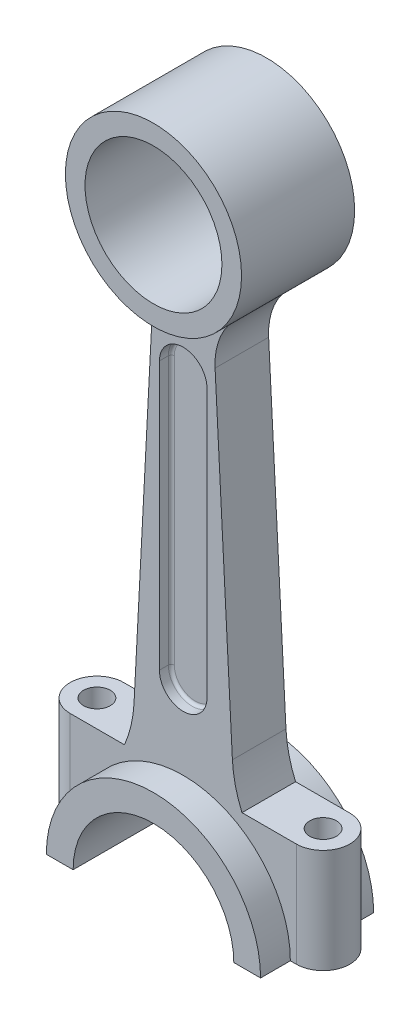
SolidWorks part; units mm, degrees
ref_plane "Front Plane" through (0, 0, 0) normal (0, 0, 1) x (1, 0, 0)
ref_plane "Top Plane" through (0, 0, 0) normal (0, 1, 0) x (1, 0, 0)
ref_plane "Right Plane" through (0, 0, 0) normal (1, 0, 0) x (0, 0, -1)
sketch "Sketch1" plane through (0, 0, 0) normal (0, 0, 1) x (1, 0, 0)
  line L0 (0, 0) -> (0, -201.2) construction
  line L1 (-10, -27.865) -> (-17.4334, -169.7028)
  line L2 (10, -27.865) -> (17.4334, -169.7028)
  line L3 (-36, -201.2) -> (-27, -201.2)
  line L4 (27, -201.2) -> (36, -201.2)
  circle A0 centre (0, 0) radius 29.6051
  circle A1 centre (0, 0) radius 23.004
  arc A2 (27, -201.2) -> (-27, -201.2) centre (0, -201.2) ccw
  arc A3 (36, -201.2) -> (-36, -201.2) centre (0, -201.2) ccw
  dimension "D1" = 201.2
  dimension "D4" = 36
  dimension "D5" = 27
  dimension "D2" = 20
  dimension "D3" = 6
extrude "Boss-Extrude1" add sketch "Sketch1" along normal mid plane 38 contours A3 A2 | A1 A0 | A3 L3 A2 L4 region at (-16.5536, 23.5279, 0) region at (0, -166.005, 0)
extrude "Boss-Extrude2" add sketch "Sketch1<3>" along normal mid plane 18 contours A0 L0 A3 L2 | L0 A0 L1 A3 region at (7.0586, -103.8971, 0) region at (-7.0586, -103.8971, 0)
sketch "Sketch1<3>" plane through (0, 0, 0) normal (0, 0, 1) x (1, 0, 0) same geometry as "Sketch1"
sketch "Sketch2" plane through (0, 0, -9) normal (0, 0, -1) x (-1, 0, 0)
  line L0 (0, 0) -> (0, -201.2) construction
  line L1 (0, -138.6117) -> (0, -48.6117) construction
  line L2 (-8, -138.6117) -> (-8, -48.6117)
  line L3 (8, -138.6117) -> (8, -48.6117)
  arc A0 (-8, -138.6117) -> (8, -138.6117) centre (0, -138.6117) ccw
  arc A1 (8, -48.6117) -> (-8, -48.6117) centre (0, -48.6117) ccw
  point P6 (0, -93.6117)
  dimension "D2" = 8
  dimension "D1" = 90
extrude "Cut-Extrude1" cut sketch "Sketch2" against normal blind 4
mirror "Mirror1" about plane through (0, 0, 0) normal (0, 0, 1) of "Cut-Extrude1"
fillet "Fillet1" radius 1 8 edges at (8, -93.6117, -5) (0, -40.6117, -5) (-8, -93.6117, -5) (0, -146.6117, -5) (-8, -93.6117, 5) (0, -40.6117, 5) (8, -93.6117, 5) (0, -146.6117, 5)
fillet "Fillet2" radius 40 2 edges at (17.4334, -169.7028, 0) (-17.4334, -169.7028, 0)
combine bodies "Combine1" operation type add bodies to combine 107 105
fillet "Fillet4" radius 22.5 2 edges at (10, -27.865, 0) (-10, -27.865, 0)
ref_plane "Plane1" through (0, -166.2, 0) normal (0, 1, 0) x (1, 0, 0)
sketch "Sketch3" plane through (0, -166.2, 0) normal (0, 1, 0) x (1, 0, 0)
  line L0 (-38, 0) -> (38, 0) construction
  line L1 (-38, 9) -> (38, 9)
  line L2 (-38, -9) -> (38, -9)
  arc A0 (-38, 9) -> (-38, -9) centre (-38, 0) ccw
  arc A1 (38, -9) -> (38, 9) centre (38, 0) ccw
  point P2 (0, 0)
  dimension "D2" = 9
  dimension "D1" = 76
extrude "Boss-Extrude3" add sketch "Sketch3" along normal up to surface (-35 mm away) up to face at (-31.5, -201.2, 0)
sketch "Sketch5" plane through (0, 0, 9) normal (0, 0, 1) x (1, 0, 0)
  line L1 (-27, -201.2) -> (27, -201.2)
  line L2 (-27, -201.2) -> (27, -201.2)
  arc A1 (27, -201.2) -> (-27, -201.2) centre (0, -201.2) ccw
  arc A2 (27, -201.2) -> (-27, -201.2) centre (0, -201.2) ccw
  dimension "D1" = 0
extrude "Cut-Extrude2" cut sketch "Sketch5" against normal through all
sketch "Sketch6" plane through (0, -166.2, 0) normal (0, 1, 0) x (1, 0, 0)
  line L0 (0, 0) -> (-52.9255, 0) construction
  line L1 (0, 0) -> (55.2334, 0) construction
  circle A4 centre (-38, 0) radius 4.5
  circle A5 centre (38, 0) radius 4.5
  dimension "D1" = 38
  dimension "D3" = 9
  dimension "D2" = 38
extrude "Cut-Extrude3" cut sketch "Sketch6" against normal through all
